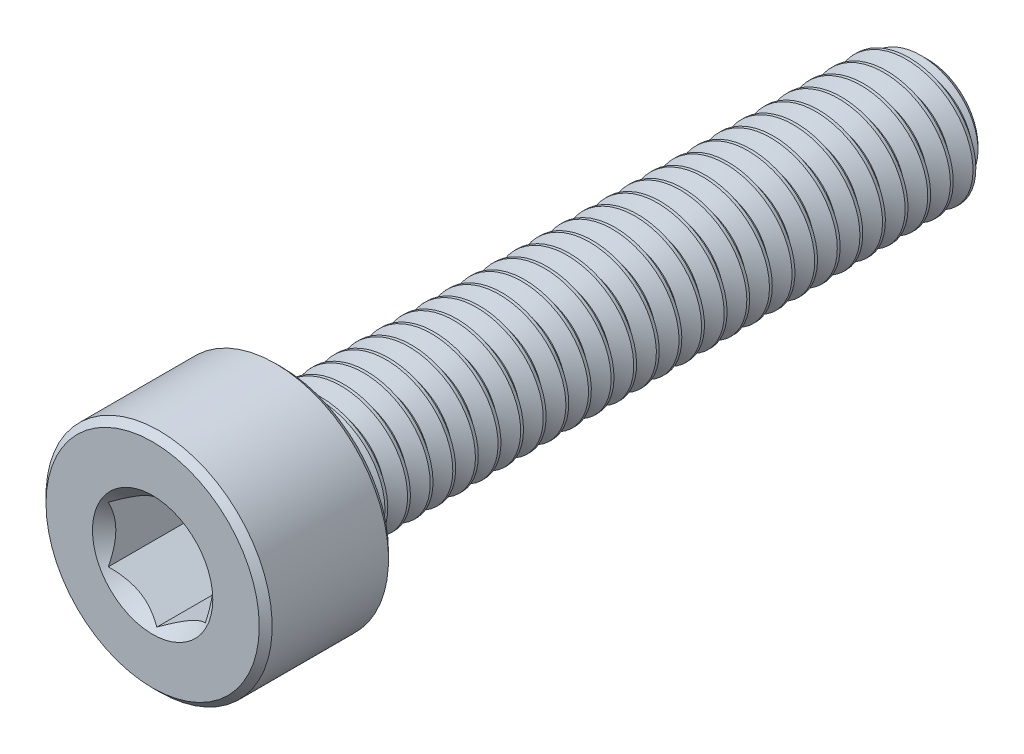
SolidWorks part; units mm, degrees
ref_plane "Front Plane" through (0, 0, 0) normal (0, 0, 1) x (1, 0, 0)
ref_plane "Top Plane" through (0, 0, 0) normal (0, 1, 0) x (1, 0, 0)
ref_plane "Right Plane" through (0, 0, 0) normal (1, 0, 0) x (0, 0, -1)
sketch "Sketch1" plane through (0, 0, 0) normal (1, 0, 0) x (0, 0, -1)
  line L0 (-12, 0) -> (12, 0) construction
  line L1 (12, 0) -> (12, 1.5453) construction
  line L2 (12, 1.5453) -> (11.5453, 2) construction
  line L3 (11.5453, 2) -> (11.475, 2) construction
  line L4 (11.475, 2) -> (-8, 2) construction
  line L5 (-8, 2) -> (-8, 3.5) construction
  line L6 (-8, 3.5) -> (-12, 3.5) construction
  line L7 (-12, 3.5) -> (-12, 0) construction
  line L8 (12, 1.5453) -> (12, 2) construction
  line L9 (11.9563, 2.0758) -> (12.3063, 1.4696) construction
  line L10 (12.3063, 1.4696) -> (12.6563, 2.0758) construction
  line L11 (12.6563, 2.0758) -> (11.9563, 2.0758) construction
  line L12 (12.3063, 2.0758) -> (12.3063, 2) construction
  line L13 (12.3063, 1.4696) -> (12.3063, 1.5453) construction
  line L14 (12.2625, 1.5453) -> (12.35, 1.5453) construction
  line L15 (12, 2) -> (12.6125, 2) construction
  line L16 (11.9781, 2.0379) -> (12.6344, 2.0379) construction
  line L17 (12, 0) -> (12, -2) construction
  line L18 (-8.2, 3.5) -> (-8, 3.3) construction
  line L19 (-11.8, 3.5) -> (-12, 3.3) construction
  line L20 (-8, 2) -> (-8, 0) construction
  line L21 (-8, 1) -> (-1.3333, 1) construction
  line L22 (-1.3333, 1) -> (5.3333, 1) construction
  line L23 (5.3333, 1) -> (12, 1) construction
  line L24 (-1.3333, 1) -> (-1.3333, 2) construction
  line L25 (-1.3333, 2) -> (-1.3333, 3.5) construction
  line L26 (5.3333, 1) -> (5.3333, 3.5) construction
  point P0 (-12, 1.5)
  point P3 (10.25, 2)
  point P4 (0, 0)
  point P18 (5.3333, 2)
  point P22 (12.3063, 1.5453)
  point P24 (11.475, 2)
  point P25 (12.3063, 2)
  point P28 (12.3063, 2.0379)
  point P29 (10.25, -2)
  point P30 (-1.3333, 2)
  point P31 (-10, 3.5)
  point P37 (-8.7, 3.5)
  point P38 (-11.7, 3.5)
  point P45 (-1.3333, 1)
  point P46 (5.3333, 1)
  dimension "D2" = 0.0875
  dimension "D7" = 0.2
  dimension "D8" = 0.2
  dimension "D9" = 0.2
  dimension "D10" = 0.1
  dimension "D11" = 0.5
  dimension "Drive Size" = 3
  dimension "Head Diameter" = 7
  dimension "Head Height" = 4
  dimension "Thread Pitch" = 0.7
  dimension "Thread Dia" = 4
  dimension "Length" = 20
  dimension "D12" = 0.525
  dimension "D4" = 1.75
  dimension "D3" = 45
sketch "Sketch2" plane through (0, 0, 0) normal (1, 0, 0) x (0, 0, -1)
  line L0 (-12, 0) -> (-12, 3.3)
  line L1 (-11.8, 3.5) -> (-8.2, 3.5)
  line L2 (-8, 3.3) -> (-8, 2.2)
  line L4 (11.5453, 2) -> (12, 1.5453)
  line L5 (12, 1.5453) -> (12, 0)
  line L6 (-8, 3.5) -> (-12, 3.5) construction
  line L7 (12, 0) -> (-12, 0)
  line L8 (-11.8, 3.5) -> (-12, 3.3) construction
  line L10 (-11.8, 3.5) -> (-12, 3.3)
  line L14 (-8.2, 3.5) -> (-8, 3.3) construction
  line L16 (-8.2, 3.5) -> (-8, 3.3)
  line L17 (-8, 2) -> (-8, 3.5) construction
  line L19 (-7.8, 2) -> (11.5453, 2)
  line L20 (11.475, 2) -> (-8, 2) construction
  arc A1 (-8, 2.2) -> (-7.8, 2) centre (-7.8, 2.2) ccw
  dimension "D3" = 0.2
revolve "Revolve1" add sketch "Sketch2" angle 360 about L7
sketch "Sketch3" plane through (0, 0, 12) normal (0, 0, 1) x (1, 0, 0)
  line L1 (1.5, -0.866) -> (1.5, 0.866)
  line L2 (1.5, 0.866) -> (0, 1.7321)
  line L3 (0, 1.7321) -> (-1.5, 0.866)
  line L4 (-1.5, 0.866) -> (-1.5, -0.866)
  line L5 (-1.5, -0.866) -> (0, -1.7321)
  line L6 (0, -1.7321) -> (1.5, -0.866)
  circle A0 centre (0, 0) radius 1.5 construction
  circle A1 centre (0, 0) radius 3.5 construction
  circle A2 centre (0, 0) radius 3.5 construction
  circle A3 centre (0, 0) radius 1.7321 construction
  point P13 (0, 0)
  dimension "D1" = 3.4641
extrude "Cut-Extrude1" cut sketch "Sketch3" against normal offset from surface (3 mm away) 1 up to face at (0, 3.3, 8)
sketch "Sketch4" plane through (0, 0, 12) normal (0, 0, 1) x (1, 0, 0)
  circle A0 centre (0, 0) radius 1.862
  dimension "D1" = 3.7239
extrude "Cut-Extrude2" cut sketch "Sketch4" against normal up to vertex (2 mm away) draft 45 up to point (0, 3.5, 10)
sketch "Sketch11" plane through (0, 0, 0) normal (1, 0, 0) x (0, 0, -1)
  line L0 (-12, 0) -> (12, 0) construction
  line L1 (-12, 0) -> (12, 0) construction
  line L2 (-4.25, 0) -> (-4.25, 2) construction
  line L3 (11.475, 2) -> (-8, 2) construction
  line L4 (8.25, 0) -> (8.25, 2) construction
  line L6 (12, 1.5453) -> (12, 2) construction
  point P2 (-4.25, 0)
  point P3 (8.25, 0)
  dimension "D1" = 3.75
  dimension "D2" = 3.75
sketch "Sketch6" plane through (0, 0, -12) normal (0, 0, -1) x (-1, 0, 0)
  circle A0 centre (0, 0) radius 2
curve "Helix/Spiral1" pitch 0.7 height 20.7 radius 2 centre (0, 0, -12) axis (0, 0, 1) start towards (0, 1, 0)
sketch "Sketch10" plane through (0, 0, 0) normal (1, 0, 0) x (0, 0, -1)
  line L0 (-7.8, -3.5) -> (-7.8, 3.5)
  line L5 (-12, 0) -> (12, 0) construction
  line L6 (-7.8, 2) -> (-7.8, -2) construction
  point P3 (-7.8, 0)
split "Split1" trim tools "Sketch10" bodies to split 106 resulting bodies 114 115
sketch "Sketch7" plane through (0, 0, 0) normal (1, 0, 0) x (0, 0, -1)
  line L0 (11.9781, 2.0379) -> (12.6344, 2.0379)
  line L1 (12.6344, 2.0379) -> (12.35, 1.5453)
  line L2 (12.35, 1.5453) -> (12.2625, 1.5453)
  line L3 (12.2625, 1.5453) -> (11.9781, 2.0379)
sweep "Cut-Sweep1" cut profiles "Sketch7" path "Helix/Spiral1" align with end faces yes
sketch "Sketch8" plane through (0, 0, 0) normal (1, 0, 0) x (0, 0, -1)
  line L0 (-8, 0) -> (-8, 2)
  line L1 (-7.8, -2) -> (-7.8, 2) construction
  line L2 (-8, 2) -> (-7.8, 2)
  line L4 (-7.8, 2) -> (-6.6453, 0)
  line L5 (-6.6453, 0) -> (-8, 0)
  line L6 (11.475, 2) -> (-8, 2) construction
  line L7 (-12, 0) -> (12, 0) construction
  dimension "D1" = 60
revolve "Revolve2" add sketch "Sketch8" angle 360 about L5
equation "\"D2@Sketch1\" = \"Thread Pitch@Sketch1\" / 8"
equation "\"D4@Helix/Spiral1\" = \"Thread Pitch@Sketch1\""
equation "\"D7@Sketch1\" = \"Head Height@Sketch1\" * .05"
equation "\"D8@Sketch1\"=\"D7@Sketch1\""
equation "\"D9@Sketch1\"=\"D7@Sketch1\""
equation "\"D10@Sketch1\"=\"D7@Sketch1\"/2"
equation "\"D11@Sketch1\"=\"D10@Sketch1\"*5"
equation "\"D4@Sketch1\"=\"Thread Pitch@Sketch1\"*2.5"
equation "\"D12@Sketch1\"=\"Thread Pitch@Sketch1\"*.75"
equation "\"D3@Helix/Spiral1\"=\"Length@Sketch1\"+\"Thread Pitch@Sketch1\""
equation "\"D3@Sketch2\"=\"Thread Dia@Sketch1\"*0.05"
equation "\"D1@Sketch11\"=\"Length@Sketch1\"*0.1875"
equation "\"D2@Sketch11\"=\"D1@Sketch11\""
equation "\"D1@Sketch4\"=\"D1@Sketch3\"*1.075"
